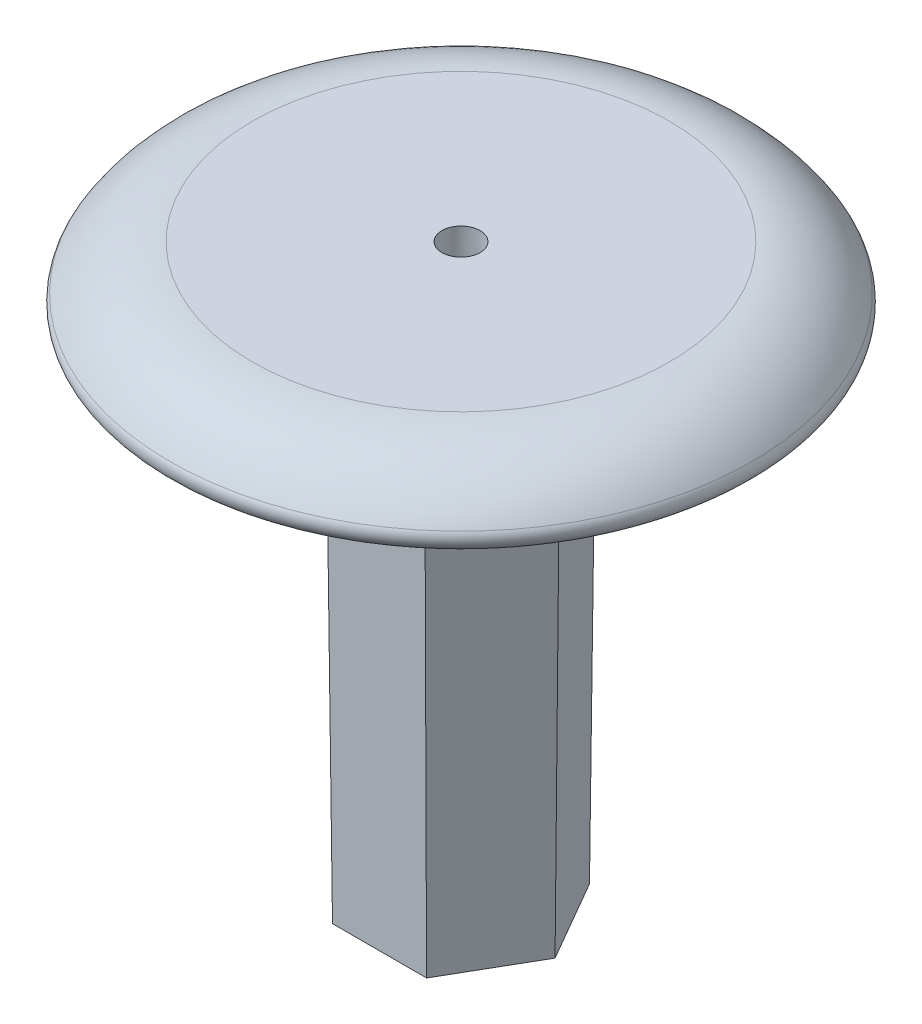
SolidWorks part; units mm, degrees
note: '?' marks a value the reader was unsure of.
ref_plane "Plane1" through (0, 0, 0) normal (0, 0, 1) x (1, 0, 0)
ref_plane "Plane2" through (0, 0, 0) normal (0, 1, 0) x (1, 0, 0)
ref_plane "Plane3" through (0, 0, 0) normal (1, 0, 0) x (0, 0, -1)
sketch "Sketch1" plane through (0, 0, 0) normal (0, 0, 1) x (1, 0, 0)
  line L0 (0, 0) -> (10.9104, 0)
  line L1 (8.128, 2.54) -> (0, 2.54)
  line L2 (0, 2.54) -> (0, 0)
  line L3 (0, 2.54) -> (0, 0) construction
  arc A0 (10.9104, 0) -> (11.3385, 0.7815) centre (10.9104, 0.508) ccw
  arc A1 (11.3385, 0.7815) -> (8.128, 2.54) centre (8.128, -1.27) ccw
  dimension "D2" = 3.81
  dimension "D3" = 0.508
  dimension "D1" = 2.54
  dimension "D4" = 8.128
revolve "Head" add sketch "Sketch1" angle 360 about L3
sketch "Sketch2" plane through (0, 2.54, 0) normal (0, 1, 0) x (-1, 0, 0)
  line L0 (1.8331, -3.175) -> (-1.8331, -3.175)
  line L1 (0, 0) -> (-7.9329, 0) construction
  line L2 (-3.6662, 0) -> (-1.8331, -3.175)
  line L3 (0, 0) -> (0, -6.656) construction
  line L4 (3.6662, 0) -> (1.8331, -3.175)
  line L5 (3.6662, 0) -> (1.8331, 3.175)
  line L6 (-3.6662, 0) -> (-1.8331, 3.175)
  line L7 (1.8331, 3.175) -> (-1.8331, 3.175)
  dimension "D1" = 6.35
  dimension "D2" = 6.35
extrude "Shaft" add sketch "Sketch2" against normal blind 22.352
draft "Draft on Shaft" type of draft neutral plane draft angle 0.5 faces to draft 6 face at (0, -9.906, 3.175) face at (2.7496, -9.906, 1.5875) face at (2.7496, -9.906, -1.5875) face at (0, -9.906, -3.175) face at (-2.7496, -9.906, -1.5875) face at (-2.7496, -9.906, 1.5875) neutral plane through (5.4993, -19.812, 3.175) neutral plane normal (0, -1, 0) parameters "D1"=0.5
sketch "Sketch3" plane through (0, -19.812, 0) normal (0, -1, 0) x (1, 0, 0)
  circle A0 centre (0, 0) radius 1.524
  dimension "D1" = 3.048
extrude "Thru Hole" cut sketch "Sketch3" against normal through all draft 2
fillet "Fillet1" radius 1.27 6 edges at (0, 0, -3.3479) (-2.8994, 0, -1.6739) (-2.8994, 0, 1.6739) (0, 0, 3.3479) (2.8994, 0, 1.6739) (2.8994, 0, -1.6739)
ref_axis "Axis1" through (0, -69.812, 0) along (0, 1, 0)?
